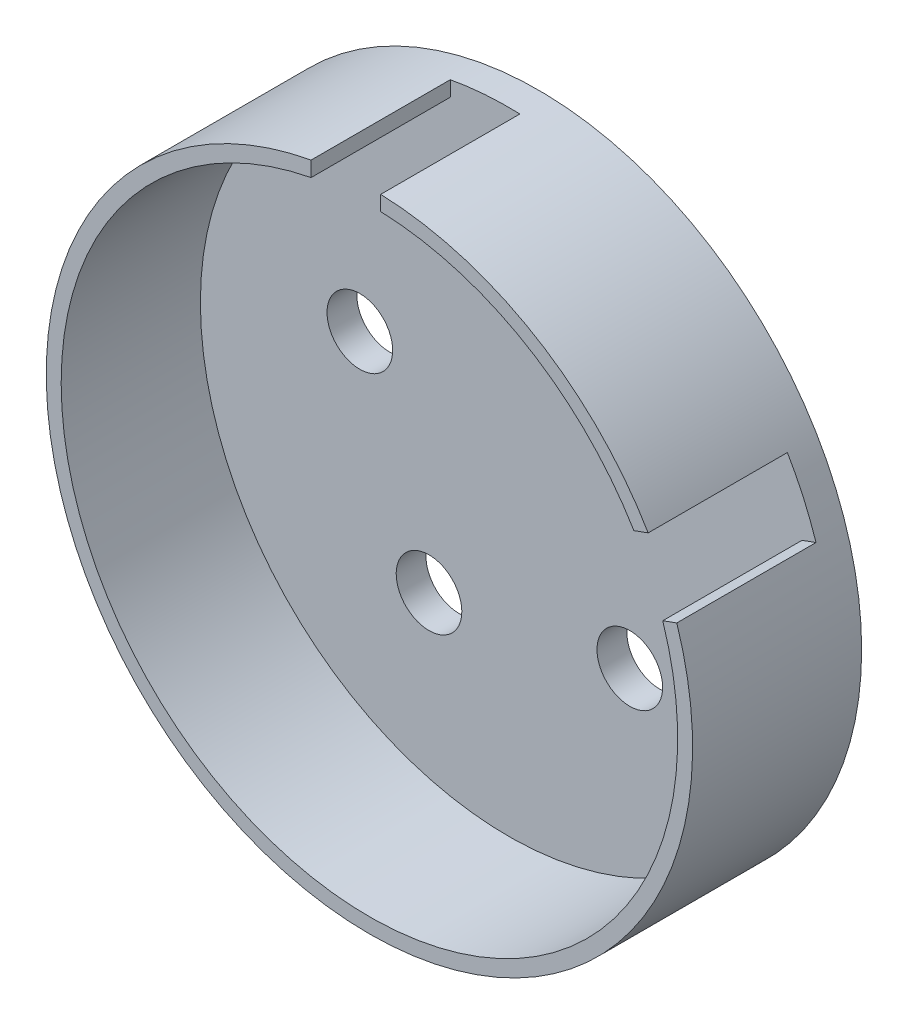
SolidWorks part; units mm, degrees
note: '?' marks a value the reader was unsure of.
ref_plane "Plan de face" through (0, 0, 0) normal (0, 0, 1) x (1, 0, 0)
ref_plane "Plan de dessus" through (0, 0, 0) normal (0, 1, 0) x (1, 0, 0)
ref_plane "Plan de droite" through (0, 0, 0) normal (1, 0, 0) x (0, 0, -1)
sketch "Esquisse1" plane through (0, 0, 0) normal (0, 0, 1) x (1, 0, 0)
  circle A0 centre (0, 0) radius 32.5
  dimension "D1" = 65
extrude "Boss.-Extru.1" add sketch "Esquisse1" along normal blind 17
sketch "Esquisse2" plane through (0, 0, 17) normal (0, 0, 1) x (1, 0, 0)
  circle A0 centre (0, 0) radius 31
  dimension "D1" = 62
extrude "Enlèv. mat.-Extru.1" cut sketch "Esquisse2" against normal blind 14
sketch "Esquisse3" plane through (0, 0, 17) normal (0, 0, 1) x (1, 0, 0)
  line L1 (1.1329, 42.2821) -> (-5.8671, 42.2821)
  line L2 (1.1329, 42.2821) -> (1.1329, 21.2754)
  line L3 (1.1329, 21.2754) -> (-5.8671, 21.2754)
  line L4 (-5.8671, 42.2821) -> (-5.8671, 21.2754)
  dimension "D1" = 7
extrude "Enlèv. mat.-Extru.2" cut sketch "Esquisse3" against normal blind 14
ref_axis "Axe1" through (0, 0, 17) along (0, 0, -1)?
pattern_circular "Répétition circulaire1" count 2 every 70 about axis through (0, 0, 17) along (0, 0, -1) of "Enlèv. mat.-Extru.2"
hole_wizard "Dégagement M61" positions "Esquisse5" profile "Esquisse4" hole size "M6" standard "JIS" end condition through all
sketch "Esquisse5" plane through (0, 0, 3) normal (0, 0, 1) x (1, 0, 0)
  point P0 (-14.965, 5.494)
sketch "Esquisse4" plane through (-14.965, 5.494, 3) normal (1, 0, 0) x (0, -1, 0)
  line L0 (0, 0) -> (0, 3)
  line L1 (0, 3) -> (3.3, 3)
  line L2 (3.3, 3) -> (3.3, 0)
  line L5 (3.3, 0) -> (0, 0)
  line L11 (0, -6.35) -> (0, 107.95) construction
  dimension "Diamètre du perçage jusqu'au prochain" = 6.6
  dimension "Profondeur du perçage jusqu'au prochain" = 3
pattern_circular "Répétition circulaire2" count 3 every 80 about axis through (0, 0, 0) along (0, 0, 1) of "Dégagement M61"
